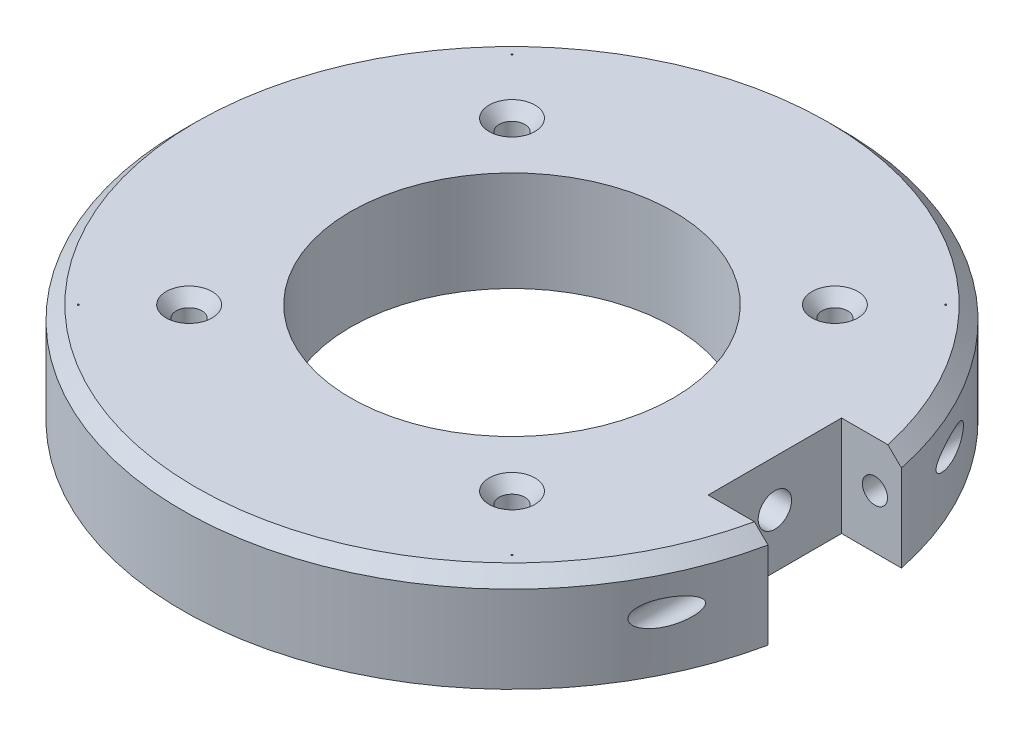
SolidWorks part; units mm, degrees
material "Chrome Stainless Steel"
ref_plane "Front Plane" through (0, 0, 0) normal (0, 0, 1) x (1, 0, 0)
ref_plane "Top Plane" through (0, 0, 0) normal (0, 1, 0) x (1, 0, 0)
ref_plane "Right Plane" through (0, 0, 0) normal (1, 0, 0) x (0, 0, -1)
sketch "Sketch1" plane through (0, 0, 0) normal (0, 0, 1) x (1, 0, 0)
  line L0 (0, 0) -> (31.369, 0)
  line L1 (31.369, 0) -> (31.369, 8.255)
  line L2 (31.369, 8.255) -> (30.099, 9.525)
  line L3 (30.099, 9.525) -> (0, 9.525)
  line L4 (0, 9.525) -> (0, 0) construction
  line L5 (0, 0) -> (0, 9.525)
  dimension "D1" = 9.525
  dimension "D2" = 45
  dimension "D3" = 1.27
  dimension "D4" = 31.369
revolve "Revolve1" add sketch "Sketch1" angle 360 about L4
sketch "Sketch2" plane through (0, 0, 0) normal (0, -1, 0) x (1, 0, 0)
  circle A0 centre (0, 0) radius 15.367
  dimension "D1" = 30.734
extrude "Cut-Extrude1" cut sketch "Sketch2" against normal through all
sketch "Sketch3" plane through (0, 0, 0) normal (0, -1, 0) x (1, 0, 0)
  line L1 (-15.367, 15.367) -> (15.367, 15.367)
  line L2 (-15.367, 15.367) -> (-15.367, -15.367)
  line L3 (-15.367, -15.367) -> (15.367, -15.367)
  line L4 (15.367, 15.367) -> (15.367, -15.367)
  line L5 (-15.367, 15.367) -> (15.367, -15.367) construction
  line L6 (-15.367, -15.367) -> (15.367, 15.367) construction
  point P0 (0, 0)
  dimension "D1" = 30.734
hole_wizard "CSK for #2 Flat Head Machine Screw (100)1" positions "Sketch6" profile "Sketch5" countersink size "#2" standard "ANSI Inch" end condition through all
sketch "Sketch6" plane through (0, 9.525, 0) normal (0, 1, 0) x (1, 0, 0)
  point P0 (-15.367, 15.367)
  point P3 (15.367, 15.367)
  point P6 (15.367, -15.367)
  point P9 (-15.367, -15.367)
sketch "Sketch5" plane through (-15.367, 9.525, -15.367) normal (1, 0, 0) x (0, 0, 1)
  line L0 (0, 0) -> (0, 9.525)
  line L1 (0, 9.525) -> (1.2192, 9.525)
  line L2 (1.2192, 9.525) -> (1.2192, 1.1103)
  line L3 (1.2192, 1.1103) -> (2.1844, 0)
  line L5 (2.1844, 0) -> (0, 0)
  line L6 (-1.2192, 1.1103) -> (-2.1844, 0) construction
  line L11 (0, -6.35) -> (0, 107.95) construction
  dimension "Thru Hole Dia." = 2.4384
  dimension "Thru Hole Depth" = 9.525
  dimension "Near C'Sink Dia." = 4.3688
  dimension "Near C'Sink Angle" = 82
sketch "Sketch8" plane through (0, 9.525, 0) normal (0, 1, 0) x (1, 0, 0)
  line L0 (15.367, 0) -> (31.369, 0) construction
  line L1 (31.369, 6.35) -> (31.369, -6.35)
  line L2 (31.369, -6.35) -> (25.019, -6.35)
  line L3 (25.019, -6.35) -> (25.019, 6.35)
  line L4 (31.369, 6.35) -> (25.019, 6.35)
  circle A0 centre (0, 0) radius 15.367 construction
  circle A1 centre (0, 0) radius 31.369 construction
  point P11 (25.019, 0)
  dimension "D1" = 6.35
  dimension "D2" = 12.7
extrude "Cut-Extrude2" cut sketch "Sketch8" against normal through all
sketch "Sketch14" plane through (0, 0, 6.35) normal (0, 0, -1) x (-1, 0, 0)
  line L0 (-30.7196, 0) -> (-25.019, 0) construction
  line L1 (-25.019, 0) -> (-25.019, 9.525) construction
  circle A0 centre (-28.194, 5.1181) radius 1.1938
  point P3 (-27.8693, 0)
  dimension "D1" = 5.1181
  dimension "D2" = 3.175
extrude "Cut-Extrude3" cut sketch "Sketch14" against normal through all and the other way through all
ref_axis "Axis1" through (28.194, 5.1181, 16.3717) along (0, 0, -1)
sketch "Sketch16" plane through (25.019, 0, 0) normal (1, 0, 0) x (0, 0, -1)
  line L0 (-6.35, 5.1181) -> (6.35, 5.1181) construction
  line L1 (-16.3717, 5.1181) -> (19.3506, 5.1181) construction
  line L2 (-6.35, 0) -> (-6.35, 9.525) construction
  line L3 (6.35, 8.255) -> (6.35, 0) construction
  point P8 (0, 5.1181)
hole_wizard "1/8 (0.125) Diameter Hole1" positions "Sketch18" profile "Sketch17" hole size "1/8" standard "ANSI Inch"
sketch "Sketch18" plane through (25.019, 0, 0) normal (1, 0, 0) x (0, 0, -1)
  point P0 (0, 5.1181)
sketch "Sketch17" plane through (25.019, 5.1181, 0) normal (0, 1, 0) x (0, 0, -1)
  line L0 (0, 0) -> (0, 8.2776)
  line L1 (0, 8.2776) -> (1.5875, 7.62)
  line L2 (1.5875, 7.62) -> (1.5875, 0)
  line L5 (1.5875, 0) -> (0, 0)
  line L10 (0, 8.2776) -> (-1.5875, 7.62) construction
  line L11 (0, -6.35) -> (0, 107.95) construction
  dimension "Hole Dia." = 3.175
  dimension "Hole Depth" = 7.62
  dimension "Drill Angle" = 135
sketch "Sketch19" plane through (0, 0, 0) normal (0, -1, 0) x (1, 0, 0)
  line L1 (-20.6375, 20.6375) -> (20.6375, 20.6375)
  line L2 (-20.6375, 20.6375) -> (-20.6375, -20.6375)
  line L3 (-20.6375, -20.6375) -> (20.6375, -20.6375)
  line L4 (20.6375, 20.6375) -> (20.6375, -20.6375)
  line L5 (-20.6375, 20.6375) -> (20.6375, -20.6375) construction
  line L6 (-20.6375, -20.6375) -> (20.6375, 20.6375) construction
  point P0 (0, 0)
  dimension "D1" = 41.275
hole_wizard "#4-40 Tapped Hole1" positions "Sketch21" profile "Sketch20" tap size "#4-40" standard "ANSI Inch"
sketch "Sketch21" plane through (0, 0, 0) normal (0, -1, 0) x (-1, 0, 0)
  point P0 (-20.6375, -20.6375)
  point P3 (-20.6375, 20.6375)
  point P6 (20.6375, 20.6375)
  point P9 (20.6375, -20.6375)
sketch "Sketch20" plane through (20.6375, 0, 20.6375) normal (1, 0, 0) x (0, 0, -1)
  line L0 (0, 0) -> (0, 9.5692)
  line L1 (0, 9.5692) -> (1.1303, 8.89)
  line L2 (1.1303, 8.89) -> (1.1303, 0.4572)
  line L3 (1.1303, 0.4572) -> (1.5875, 0)
  line L5 (1.5875, 0) -> (0, 0)
  line L6 (-1.1303, 0.4572) -> (-1.5875, 0) construction
  line L10 (0, 9.5692) -> (-1.1303, 8.89) construction
  line L11 (0, -6.35) -> (0, 107.95) construction
  dimension "Tap Drill Dia." = 2.2606
  dimension "Tap Drill Depth" = 8.89
  dimension "Near C'Sink Dia." = 3.175
  dimension "Near C'Sink Angle" = 90
  dimension "Drill Angle" = 118
cosmetic thread "Hole Thread1" parameters "D1"=6.985, "D2"=2.8448
cosmetic thread "Hole Thread2" parameters "D1"=6.985, "D2"=2.8448
cosmetic thread "Hole Thread3" parameters "D1"=6.985, "D2"=2.8448
cosmetic thread "Hole Thread4" parameters "D1"=6.985, "D2"=2.8448
